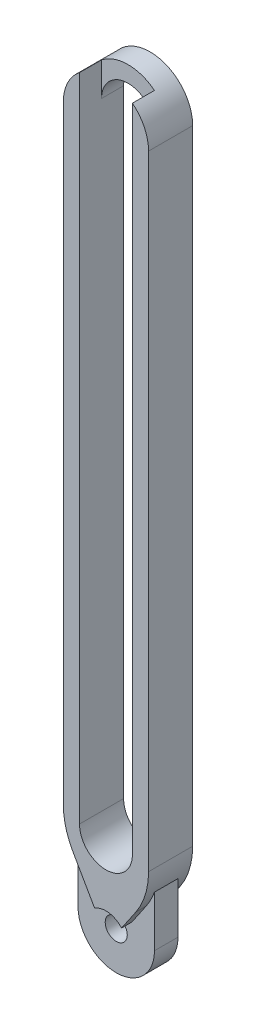
SolidWorks part; units mm, degrees
ref_plane "Piano frontale" through (0, 0, 0) normal (0, 0, 1) x (1, 0, 0)
ref_plane "Piano superiore" through (0, 0, 0) normal (0, 1, 0) x (1, 0, 0)
ref_plane "Piano destro" through (0, 0, 0) normal (1, 0, 0) x (0, 0, -1)
sketch "Schizzo1" plane through (0, 0, 0) normal (0, 0, 1) x (1, 0, 0)
  line L0 (0, 182.0114) -> (0, -37.9886) construction
  line L1 (14.5, 182.0114) -> (14.5, -37.9886)
  line L2 (-14.5, 182.0114) -> (-14.5, -37.9886)
  arc A0 (14.5, 182.0114) -> (-14.5, 182.0114) centre (0, 182.0114) ccw
  arc A1 (-14.5, -37.9886) -> (14.5, -37.9886) centre (0, -37.9886) ccw
  point P3 (0, 72.0114)
  dimension "D1" = 29
  dimension "D2" = 220
extrude "Estrusione-Estrusione1" add sketch "Schizzo1" along normal mid plane 15
sketch "Schizzo3" plane through (0, 0, 0) normal (0, 0, 1) x (1, 0, 0)
  line L0 (-14.5, -37.9886) -> (14.5, -37.9886) construction
sketch "Schizzo2" plane through (0, 0, 0) normal (0, 0, 1) x (1, 0, 0)
  line L0 (0, -40.0666) -> (0, -56.0666) construction
  line L1 (13, -40.0666) -> (13, -56.0666)
  line L2 (-13, -40.0666) -> (-13, -56.0666)
  line L3 (-14.5, -37.9886) -> (14.5, -37.9886) construction
  arc A0 (13, -40.0666) -> (-13, -40.0666) centre (0, -40.0666) ccw
  arc A1 (-13, -56.0666) -> (13, -56.0666) centre (0, -56.0666) ccw
  point P3 (0, -48.0666)
  point P8 (0, -40.76)
  dimension "D1" = 16
  dimension "D2" = 13
  dimension "D3" = 2.078
extrude "Estrusione-Estrusione2" add sketch "Schizzo2" along normal mid plane 8
sketch "Schizzo4" plane through (0, 0, 4) normal (0, 0, 1) x (1, 0, 0)
  line L0 (13, -56.0666) -> (0, -56.0666) construction
  line L1 (5.2945, -51.4875) -> (14.5, -37.9886)
  line L2 (14.5, -37.9886) -> (21.4943, -44.738)
  line L3 (-3.8458, -50.2177) -> (-14.5, -31.5622)
  line L4 (-14.5, -31.5622) -> (-28.5961, -39.4536)
  line L5 (-28.5961, -39.4536) -> (-5.2945, -60.6458)
  line L6 (-14.5, 182.0114) -> (-14.5, -37.9886) construction
  line L7 (21.4943, -44.738) -> (5.3865, -60.5371)
  arc A0 (-5.2945, -60.6458) -> (5.3865, -60.5371) centre (0, -56.0666) ccw
  arc A1 (-13, -44.4112) -> (13, -44.4112) centre (0, -37.9886) ccw construction
  arc A3 (5.2945, -51.4875) -> (-3.8458, -50.2177) centre (0, -56.0666) ccw
  point P4 (-3.8458, -50.2177)
  point P17 (0, 0)
  dimension "D1" = 14
extrude "Taglio-Estrusione1" cut sketch "Schizzo4" along normal through all
mirror "Specchia1" about plane through (0, 0, 0) normal (0, 0, 1) of "Taglio-Estrusione1"
sketch "Schizzo5" plane through (0, 0, 4) normal (0, 0, 1) x (1, 0, 0)
  line L0 (-13, -44.4112) -> (-13, -34.1887)
  line L1 (-3.8458, -50.2177) -> (-14.5, -31.5622) construction
  line L2 (-13, -34.1887) -> (-15.0563, -30.5881)
  line L3 (-15.0563, -30.5881) -> (-15.0563, -43.6194)
  line L4 (-15.0563, -43.6194) -> (-13, -44.4112)
  line L5 (13, -44.4112) -> (13, -40.1882)
  line L6 (14.5, -37.9886) -> (5.2945, -51.4875) construction
  line L7 (13, -40.1882) -> (17.408, -33.7244)
  line L8 (17.408, -33.7244) -> (17.408, -44.4112)
  line L9 (17.408, -44.4112) -> (13, -44.4112)
extrude "Taglio-Estrusione2" cut sketch "Schizzo5" against normal through all
fillet "Raccordo1" radius 25 2 edges at (-14.5, -31.5622, 0) (14.5, -37.9886, 0)
sketch "Schizzo6" plane through (0, 0, 4) normal (0, 0, 1) x (1, 0, 0)
  line L0 (13, -56.0666) -> (0, -56.0666) construction
hole_wizard "Foro per Vite M6.5-1" positions "Schizzo3D1" profile "Schizzo7" hole size "M6.5" standard "ISO" end condition through all
sketch3d "Schizzo3D1"
  point P0 (0, -56.0666, 4)
sketch "Schizzo7" plane through (0, -56.0666, 4) normal (1, 0, 0) x (0, -1, 0)
  line L0 (0, 0) -> (0, 11.5)
  line L1 (0, 11.5) -> (3.75, 11.5)
  line L2 (3.75, 11.5) -> (3.75, 0)
  line L5 (3.75, 0) -> (0, 0)
  line L11 (0, -6.35) -> (0, 107.95) construction
  dimension "Thru Hole Dia." = 7.5
  dimension "Thru Hole Depth" = 11.5
sketch "Schizzo8" plane through (0, 0, 0) normal (0, 0, 1) x (1, 0, 0)
  line L0 (0, 182.0114) -> (0, -27.9886) construction
  line L1 (9, 182.0114) -> (9, -27.9886)
  line L2 (-9, 182.0114) -> (-9, -27.9886)
  arc A0 (9, 182.0114) -> (-9, 182.0114) centre (0, 182.0114) ccw
  arc A1 (-9, -27.9886) -> (9, -27.9886) centre (0, -27.9886) ccw
  point P4 (0, 77.0114)
  dimension "D1" = 18
  dimension "D2" = 210
extrude "Taglio-Estrusione3" cut sketch "Schizzo8" against normal mid plane 15
sketch "Schizzo9" plane through (0, 0, 7.5) normal (0, 0, 1) x (1, 0, 0)
  line L0 (0, 182.0114) -> (0, 202.0114) construction
  line L1 (-9, 182.0114) -> (-9, 202.0114)
  line L2 (9, 182.0114) -> (9, 202.0114)
  arc A0 (-9, 182.0114) -> (9, 182.0114) centre (0, 182.0114) ccw
  arc A1 (9, 202.0114) -> (-9, 202.0114) centre (0, 202.0114) ccw
  point P4 (0, 192.0114)
  dimension "D1" = 18
  dimension "D2" = 20
extrude "Taglio-Estrusione4" cut sketch "Schizzo9" against normal blind 7.5
sketch "Schizzo10" plane through (9, 0, 0) normal (-1, 0, 0) x (0, 0, 1)
  line L0 (-7.5, 77.0114) -> (7.5, 77.0114) construction
  line L1 (-7.5, -27.9886) -> (-7.5, 182.0114) construction
  line L2 (7.5, -27.9886) -> (7.5, 193.3802) construction
sketch "Schizzo12" plane through (0, 0, -7.5) normal (0, 0, -1) x (-1, 0, 0)
  line L0 (-9.0669, 77.0114) -> (9, 77.0114) construction
  line L1 (9, 182.0114) -> (9, -27.9886) construction
